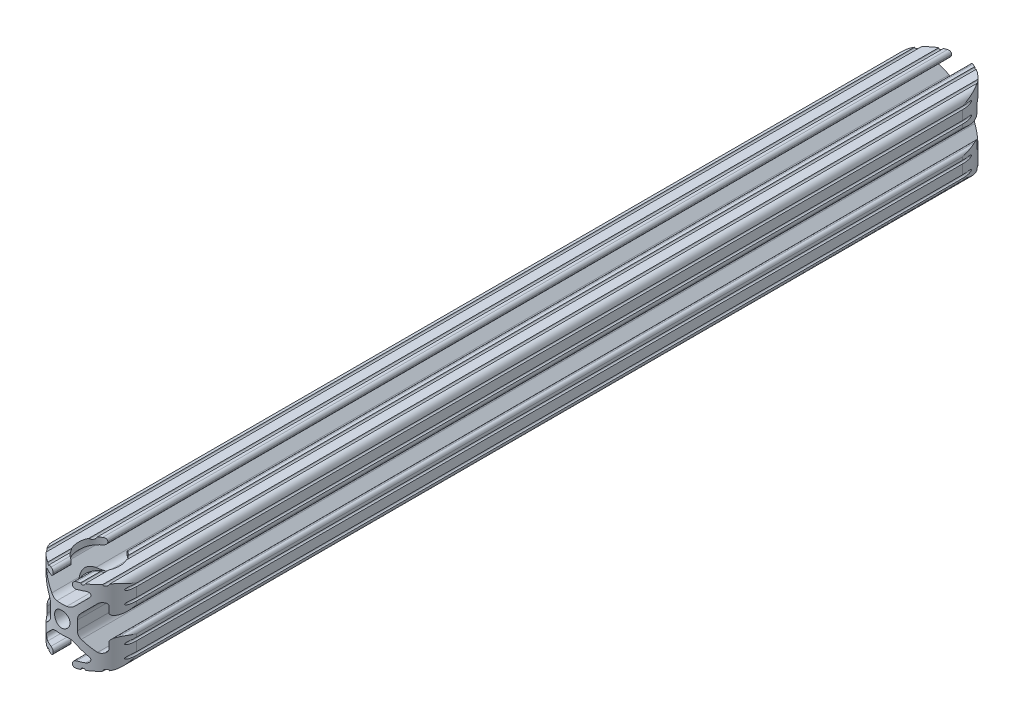
SolidWorks part; units mm, degrees
material "6063-T6"
ref_plane "Front Plane" through (0, 0, 0) normal (0, 0, 1) x (1, 0, 0)
ref_plane "Top Plane" through (0, 0, 0) normal (0, 1, 0) x (1, 0, 0)
ref_plane "Right Plane" through (0, 0, 0) normal (1, 0, 0) x (0, 0, -1)
sketch "Sketch1" plane through (0, 0, 0) normal (0, 0, 1) x (1, 0, 0)
  line L88 (-7.1797, -8.6452) -> (-3.9523, -5.4237)
  line L89 (-1.7093, -4.4958) -> (1.7093, -4.4958)
  line L90 (3.9523, -5.4237) -> (7.1797, -8.6452)
  line L91 (6.4164, -10.4902) -> (4.2875, -10.4902)
  line L92 (3.2385, -11.5392) -> (3.2385, -11.651)
  line L93 (4.2875, -12.7) -> (5.3171, -12.7)
  line L94 (6.3331, -12.7) -> (9.5504, -12.7)
  line L95 (12.7, -9.5504) -> (12.7, -6.3331)
  line L96 (12.7, -5.3171) -> (12.7, -4.2875)
  line L97 (11.651, -3.2385) -> (11.5392, -3.2385)
  line L98 (10.4902, -4.2875) -> (10.4902, -6.4021)
  line L99 (8.7371, -7.1294) -> (5.441, -3.8408)
  line L100 (4.5085, -1.5932) -> (4.5085, 1.5932)
  line L101 (5.441, 3.8408) -> (8.7371, 7.1294)
  line L102 (10.4902, 6.4021) -> (10.4902, 4.2875)
  line L103 (11.5392, 3.2385) -> (11.651, 3.2385)
  line L104 (12.7, 4.2875) -> (12.7, 5.3171)
  line L105 (12.7, 6.3331) -> (12.7, 9.5504)
  line L106 (9.5504, 12.7) -> (6.3331, 12.7)
  line L107 (5.3171, 12.7) -> (4.2875, 12.7)
  line L108 (3.2385, 11.651) -> (3.2385, 11.5392)
  line L109 (4.2875, 10.4902) -> (6.4768, 10.4902)
  line L110 (7.207, 8.7244) -> (3.8983, 5.4232)
  line L111 (1.6558, 4.4958) -> (-1.6558, 4.4958)
  line L112 (-3.8983, 5.4232) -> (-7.207, 8.7244)
  line L113 (-6.4768, 10.4902) -> (-4.2875, 10.4902)
  line L114 (-3.2385, 11.5392) -> (-3.2385, 11.651)
  line L115 (-4.2875, 12.7) -> (-5.3171, 12.7)
  line L116 (-6.3331, 12.7) -> (-9.5504, 12.7)
  line L117 (-12.7, 9.5504) -> (-12.7, 6.3331)
  line L118 (-12.7, 5.3171) -> (-12.7, 4.2875)
  line L119 (-11.651, 3.2385) -> (-11.5392, 3.2385)
  line L120 (-10.4902, 4.2875) -> (-10.4902, 6.4021)
  line L121 (-8.7371, 7.1294) -> (-5.441, 3.8408)
  line L122 (-4.5085, 1.5932) -> (-4.5085, -1.5932)
  line L123 (-5.441, -3.8408) -> (-8.7371, -7.1294)
  line L124 (-10.4902, -6.4021) -> (-10.4902, -4.2875)
  line L125 (-11.5392, -3.2385) -> (-11.651, -3.2385)
  line L126 (-12.7, -4.2875) -> (-12.7, -5.3171)
  line L127 (-12.7, -6.3331) -> (-12.7, -9.5504)
  line L128 (-9.5504, -12.7) -> (-6.3331, -12.7)
  line L129 (-5.3171, -12.7) -> (-4.2875, -12.7)
  line L130 (-3.2385, -11.651) -> (-3.2385, -11.5392)
  line L131 (-4.2875, -10.4902) -> (-6.4164, -10.4902)
  circle A1 centre (0, 0) radius 2.6035
  arc A104 (-7.1797, -8.6452) -> (-6.4164, -10.4902) centre (-6.4164, -9.4098) ccw
  arc A105 (-1.7093, -4.4958) -> (-3.9523, -5.4237) centre (-1.7093, -7.6708) ccw
  arc A106 (3.9523, -5.4237) -> (1.7093, -4.4958) centre (1.7093, -7.6708) ccw
  arc A107 (6.4164, -10.4902) -> (7.1797, -8.6452) centre (6.4164, -9.4098) ccw
  arc A108 (4.2875, -10.4902) -> (3.2385, -11.5392) centre (4.2875, -11.5392) ccw
  arc A109 (3.2385, -11.651) -> (4.2875, -12.7) centre (4.2875, -11.651) ccw
  arc A110 (6.3331, -12.7) -> (5.3171, -12.7) centre (5.8251, -12.7) ccw
  arc A111 (10.5664, -12.6998) -> (9.5504, -12.7) centre (10.0584, -12.7) ccw
  arc A112 (10.5664, -12.6998) -> (12.6998, -10.5664) centre (10.5918, -10.5918) ccw
  arc A113 (12.7, -9.5504) -> (12.6998, -10.5664) centre (12.7, -10.0584) ccw
  arc A114 (12.7, -5.3171) -> (12.7, -6.3331) centre (12.7, -5.8251) ccw
  arc A115 (12.7, -4.2875) -> (11.651, -3.2385) centre (11.651, -4.2875) ccw
  arc A116 (11.5392, -3.2385) -> (10.4902, -4.2875) centre (11.5392, -4.2875) ccw
  arc A117 (8.7371, -7.1294) -> (10.4902, -6.4021) centre (9.4628, -6.4021) ccw
  arc A118 (4.5085, -1.5932) -> (5.441, -3.8408) centre (7.6835, -1.5932) ccw
  arc A119 (5.441, 3.8408) -> (4.5085, 1.5932) centre (7.6835, 1.5932) ccw
  arc A120 (10.4902, 6.4021) -> (8.7371, 7.1294) centre (9.4628, 6.4021) ccw
  arc A121 (10.4902, 4.2875) -> (11.5392, 3.2385) centre (11.5392, 4.2875) ccw
  arc A122 (11.651, 3.2385) -> (12.7, 4.2875) centre (11.651, 4.2875) ccw
  arc A123 (12.7, 6.3331) -> (12.7, 5.3171) centre (12.7, 5.8251) ccw
  arc A124 (12.6998, 10.5664) -> (12.7, 9.5504) centre (12.7, 10.0584) ccw
  arc A125 (12.6998, 10.5664) -> (10.5664, 12.6998) centre (10.5918, 10.5918) ccw
  arc A126 (9.5504, 12.7) -> (10.5664, 12.6998) centre (10.0584, 12.7) ccw
  arc A127 (5.3171, 12.7) -> (6.3331, 12.7) centre (5.8251, 12.7) ccw
  arc A128 (4.2875, 12.7) -> (3.2385, 11.651) centre (4.2875, 11.651) ccw
  arc A129 (3.2385, 11.5392) -> (4.2875, 10.4902) centre (4.2875, 11.5392) ccw
  arc A130 (7.207, 8.7244) -> (6.4768, 10.4902) centre (6.4768, 9.4563) ccw
  arc A131 (1.6558, 4.4958) -> (3.8983, 5.4232) centre (1.6558, 7.6708) ccw
  arc A132 (-3.8983, 5.4232) -> (-1.6558, 4.4958) centre (-1.6558, 7.6708) ccw
  arc A133 (-6.4768, 10.4902) -> (-7.207, 8.7244) centre (-6.4768, 9.4563) ccw
  arc A134 (-4.2875, 10.4902) -> (-3.2385, 11.5392) centre (-4.2875, 11.5392) ccw
  arc A135 (-3.2385, 11.651) -> (-4.2875, 12.7) centre (-4.2875, 11.651) ccw
  arc A136 (-6.3331, 12.7) -> (-5.3171, 12.7) centre (-5.8251, 12.7) ccw
  arc A137 (-10.5664, 12.6998) -> (-9.5504, 12.7) centre (-10.0584, 12.7) ccw
  arc A138 (-10.5664, 12.6998) -> (-12.6998, 10.5664) centre (-10.5918, 10.5918) ccw
  arc A139 (-12.7, 9.5504) -> (-12.6998, 10.5664) centre (-12.7, 10.0584) ccw
  arc A140 (-12.7, 5.3171) -> (-12.7, 6.3331) centre (-12.7, 5.8251) ccw
  arc A141 (-12.7, 4.2875) -> (-11.651, 3.2385) centre (-11.651, 4.2875) ccw
  arc A142 (-11.5392, 3.2385) -> (-10.4902, 4.2875) centre (-11.5392, 4.2875) ccw
  arc A143 (-8.7371, 7.1294) -> (-10.4902, 6.4021) centre (-9.4628, 6.4021) ccw
  arc A144 (-4.5085, 1.5932) -> (-5.441, 3.8408) centre (-7.6835, 1.5932) ccw
  arc A145 (-5.441, -3.8408) -> (-4.5085, -1.5932) centre (-7.6835, -1.5932) ccw
  arc A146 (-10.4902, -6.4021) -> (-8.7371, -7.1294) centre (-9.4628, -6.4021) ccw
  arc A147 (-10.4902, -4.2875) -> (-11.5392, -3.2385) centre (-11.5392, -4.2875) ccw
  arc A148 (-11.651, -3.2385) -> (-12.7, -4.2875) centre (-11.651, -4.2875) ccw
  arc A149 (-12.7, -6.3331) -> (-12.7, -5.3171) centre (-12.7, -5.8251) ccw
  arc A150 (-12.6998, -10.5664) -> (-12.7, -9.5504) centre (-12.7, -10.0584) ccw
  arc A151 (-12.6998, -10.5664) -> (-10.5664, -12.6998) centre (-10.5918, -10.5918) ccw
  arc A152 (-9.5504, -12.7) -> (-10.5664, -12.6998) centre (-10.0584, -12.7) ccw
  arc A153 (-5.3171, -12.7) -> (-6.3331, -12.7) centre (-5.8251, -12.7) ccw
  arc A154 (-4.2875, -12.7) -> (-3.2385, -11.651) centre (-4.2875, -11.651) ccw
  arc A155 (-3.2385, -11.5392) -> (-4.2875, -10.4902) centre (-4.2875, -11.5392) ccw
extrude "Boss-Extrude1" add sketch "Sketch1" along normal mid plane 304.8
sketch "Sketch2" plane through (0, 12.7, 0) normal (0, 1, 0) x (1, 0, 0)
  line L0 (0, 152.4) -> (0, -152.4) construction
  line L1 (-12.7, 152.4) -> (12.7, 152.4)
  line L2 (-12.7, 152.4) -> (-12.7, -152.4)
  line L3 (-12.7, -152.4) -> (12.7, -152.4)
  line L4 (12.7, 152.4) -> (12.7, -152.4)
  circle A0 centre (0, 139.7) radius 12.7
  circle A1 centre (0, -139.7) radius 12.7
  circle A2 centre (0, -139.7) radius 3.175
  line M5 (-6.3331, 152.4) -> (-9.5504, 152.4)
  line M6 (-9.5504, 152.4) -> (-9.5504, -152.4)
  line M7 (-9.5504, -152.4) -> (-6.3331, -152.4)
  line M8 (-6.3331, -152.4) -> (-6.3331, 152.4)
  dimension "D1" = 6.35
extrude "Cut-Extrude1" cut sketch "Sketch2" against normal through all both and the other way through all contours A2 L0 | L0 A2 | A1 L2 L3 M6 | A1 M6 M7 M8 | A1 L3 M8 | A1 L3 L4 | A0 L4 L1 | A0 M8 M5 M6 | A0 L1 M8 | A0 L1 L2 M6 region at (-4.7717, 12.7, -151.8988) region at (9.8632, 12.7, -149.5632) region at (-8.1865, 12.7, -150.8688) region at (-11.3727, 12.7, -148.6456) region at (9.8632, 12.7, 149.5632) region at (1.3475, 12.7, 139.7) region at (-1.3475, 12.7, 139.7) region at (-4.7717, 12.7, 151.8988) region at (-8.1865, 12.7, 150.8688) region at (-11.3727, 12.7, 148.6456)
sketch "Sketch3" plane through (0, 12.7, 0) normal (0, 1, 0) x (1, 0, 0)
  circle A0 centre (0, -139.7) radius 6.35 construction
  circle A1 centre (0, -139.7) radius 4.8006
  circle A2 centre (0, -139.7) radius 6.985
  line M5 (6.3331, 150.7082) -> (6.3331, -150.7082)
  dimension "D1" = 12.7
  dimension "D2" = 9.6012
  dimension "D3" = 0.635
extrude "Cut-Extrude2" cut sketch "Sketch3" against normal up to vertex (8.2042 mm away) contours A1 | A0 A1 M5 | A2 M5 region at (0, 12.7, 139.7) region at (6.5949, 12.7, 139.7) region at (6.1401, 12.7, 139.7) up to point (-7.207, 8.7244, 150.157)
extrude "Cut-Extrude4" cut sketch "Sketch3<3>" along normal blind 3.9756 from surface contours A1 | A0 A1 M5 | A2 M5 region at (0, 12.7, 139.7) region at (6.5949, 12.7, 139.7) region at (6.1401, 12.7, 139.7) starting at face at (7.9961, -12.7, 0)
sketch "Sketch3<3>" plane through (0, 12.7, 0) normal (0, 1, 0) x (1, 0, 0) same geometry as "Sketch3"
extrude "Cut-Extrude5" cut sketch "Sketch3<5>" against normal up to surface (8.2042 mm away) contours A1 region at (0, 12.7, 139.7) up to face at (0, 4.4958, 147.4939)
sketch "Sketch3<5>" plane through (0, 12.7, 0) normal (0, 1, 0) x (1, 0, 0) same geometry as "Sketch3"
extrude "Cut-Extrude6" cut sketch "Sketch3<6>" along normal up to surface (8.2042 mm away) from surface contours A1 region at (0, 12.7, 139.7) up to face at (0, -4.4958, 147.4838) starting at face at (7.5504, -12.7, 46.5667)
sketch "Sketch3<6>" plane through (0, 12.7, 0) normal (0, 1, 0) x (1, 0, 0) same geometry as "Sketch3"
